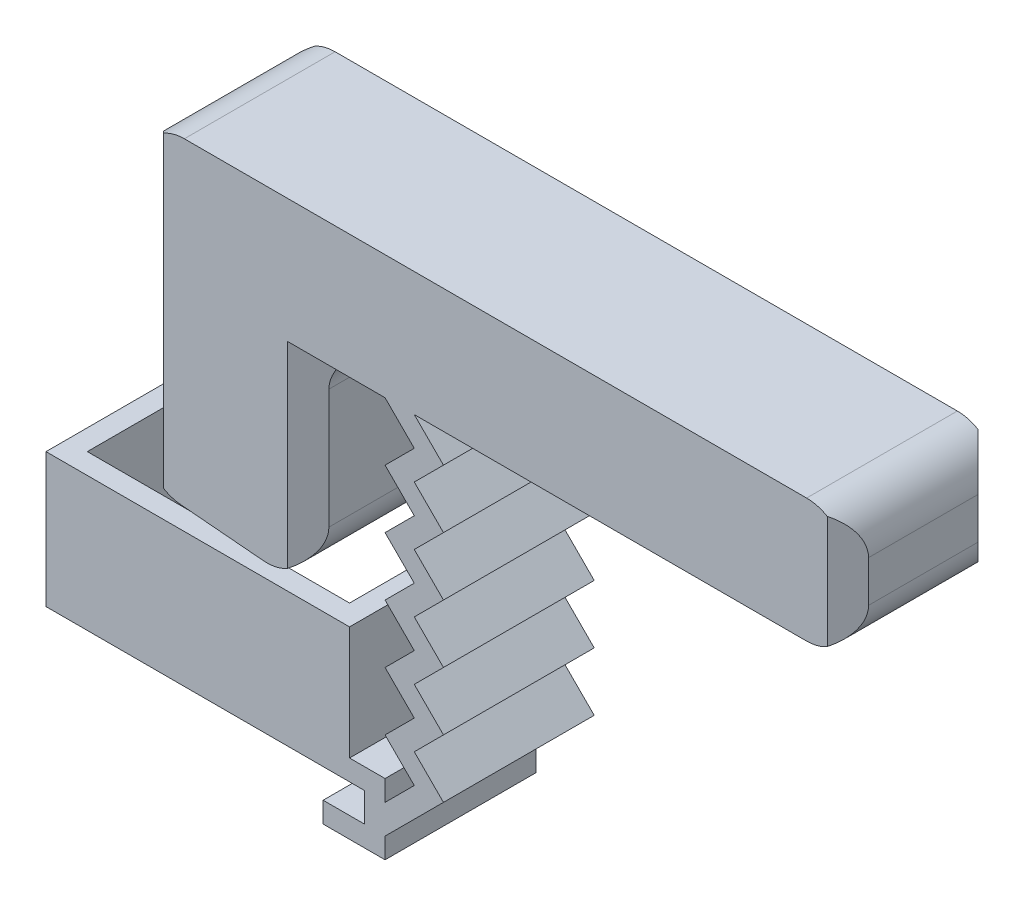
SolidWorks part; units mm, degrees
ref_plane "Front Plane" through (0, 0, 0) normal (0, 0, 1) x (1, 0, 0)
ref_plane "Top Plane" through (0, 0, 0) normal (0, 1, 0) x (1, 0, 0)
ref_plane "Right Plane" through (0, 0, 0) normal (1, 0, 0) x (0, 0, -1)
sketch "Sketch2" plane through (0, 0, 0) normal (0, 1, 0) x (1, 0, 0)
  line L0 (30.215, 56.2321) -> (30.215, 50.4321) construction
  line L1 (30.215, 50.4321) -> (17.515, 50.4321) construction
  line L2 (17.515, 50.4321) -> (17.515, 56.2321) construction
  line L3 (30.215, 56.2321) -> (30.215, 50.4321)
  line L4 (30.215, 50.4321) -> (17.515, 50.4321)
  line L5 (17.515, 50.4321) -> (17.515, 56.2321)
  line L6 (31.215, 56.7321) -> (31.215, 49.4321)
  line L7 (31.215, 49.4321) -> (16.515, 49.4321)
  line L8 (16.515, 49.4321) -> (16.515, 56.7321)
  line L11 (30.215, 56.2321) -> (29.215, 56.7321)
  line L12 (29.215, 56.7321) -> (31.215, 56.7321)
  line L14 (31.215, 56.2321) -> (31.215, 49.4321) construction
  line L15 (16.515, 49.4321) -> (16.515, 56.2321) construction
  line L16 (17.515, 56.2321) -> (18.515, 56.7321)
  line L17 (18.515, 56.7321) -> (16.515, 56.7321)
  point P2 (29.215, 56.9636)
  dimension "D2" = 1
  dimension "D3" = 0.5
  dimension "D1" = 1
extrude "Boss-Extrude3" add sketch "Sketch2" along normal blind 6.5 contours L6 L7 L8 L17 L16 L5 L4 L3 L11 L12
sketch "Sketch1" plane through (-49.4321, 0, -49.4321) normal (0, 0, 1) x (1, 0, 0)
  line L27 (82.3671, 0) -> (83.7813, 1.4142)
  line L28 (83.7813, 1.4142) -> (82.3671, 2.8284)
  line L31 (79.3671, -1.41) -> (81.3671, -1.41)
  line L32 (81.3671, -1.41) -> (81.3671, 0)
  line L33 (81.3671, 0) -> (80.6471, 0)
  line L34 (81.3671, 0) -> (61.0471, 0) construction
  line L35 (82.3671, 14.1421) -> (83.7813, 15.5563)
  line L36 (81.3671, -1.51) -> (81.3671, 0) construction
  line L37 (79.3671, -2.41) -> (82.3671, -2.41)
  line L38 (82.3671, -2.41) -> (82.3671, -1.4142)
  line L39 (82.3671, 1) -> (80.6471, 1)
  line L40 (79.3671, -1.41) -> (79.3671, -2.41)
  line L41 (80.6471, 1) -> (80.6471, 0)
  line L42 (82.3671, 2.8284) -> (83.7813, 4.2426)
  line L43 (83.7813, 4.2426) -> (82.3671, 5.6569)
  line L44 (82.3671, 5.6569) -> (83.7813, 7.0711)
  line L45 (83.7813, 7.0711) -> (82.3671, 8.4853)
  line L46 (82.3671, 8.4853) -> (83.7813, 9.8995)
  line L47 (83.7813, 9.8995) -> (82.3671, 11.3137)
  line L48 (82.3671, 11.3137) -> (83.7813, 12.7279)
  line L49 (83.7813, 12.7279) -> (82.3671, 14.1421)
  line L50 (82.3671, -1.4142) -> (85.1955, 1.4142)
  line L52 (83.7813, 2.8284) -> (85.1955, 4.2426)
  line L53 (85.1955, 4.2426) -> (83.7813, 5.6569)
  line L54 (83.7813, 5.6569) -> (85.1955, 7.0711)
  line L55 (85.1955, 7.0711) -> (83.7813, 8.4853)
  line L56 (83.7813, 8.4853) -> (85.1955, 9.8995)
  line L57 (85.1955, 9.8995) -> (83.7813, 11.3137)
  line L58 (83.7813, 11.3137) -> (85.1955, 12.7279)
  line L59 (104.7813, 16.9706) -> (83.7813, 16.9706)
  line L60 (82.8509, -0.9304) -> (85.1955, 1.4142) construction
  line L61 (83.7813, 15.5563) -> (82.3671, 16.9706)
  line L62 (85.1955, 1.4142) -> (83.7813, 2.8284)
  line L63 (83.7813, 2.8284) -> (85.1955, 4.2426)
  line L64 (85.1955, 12.7279) -> (83.0742, 14.8492) construction
  line L65 (85.1955, 4.2426) -> (83.7813, 5.6569)
  line L66 (83.7813, 5.6569) -> (85.1955, 7.0711)
  line L67 (85.1955, 7.0711) -> (83.7813, 8.4853)
  line L68 (83.7813, 8.4853) -> (85.1955, 9.8995)
  line L69 (85.1955, 9.8995) -> (83.7813, 11.3137)
  line L70 (83.7813, 11.3137) -> (85.1955, 12.7279)
  line L71 (85.1955, 12.7279) -> (83.7813, 14.1421)
  line L72 (83.7813, 14.1421) -> (85.1955, 15.5563)
  line L73 (85.1955, 15.5563) -> (83.7813, 16.9706)
  line L74 (85.1955, 15.5563) -> (83.0742, 17.6777) construction
  line L75 (82.1438, -0.2233) -> (83.7813, 1.4142) construction
  line L77 (82.8509, -0.9304) -> (85.1955, 1.4142) construction
  line L78 (78.6471, 16.9706) -> (78.6471, 7)
  line L79 (78.6471, 7) -> (70.6471, 7.6999)
  line L80 (70.6471, 7.6999) -> (70.6471, 22.9706)
  line L81 (70.6471, 22.9706) -> (104.7813, 22.9706)
  line L82 (104.7813, 22.9706) -> (104.7813, 16.9706)
  line L83 (82.3671, 16.9706) -> (78.6471, 16.9706)
  line L84 (82.3671, 0) -> (82.3671, 1)
  line L85 (82.3671, -2.41) -> (82.3671, 1) construction
  line L86 (85.1955, 1.4142) -> (83.7813, 2.8284) construction
  point P8 (105.7381, 16.9706)
  point P60 (70.6471, 10.3146)
  point P61 (105.9033, 19.9706)
  point P63 (108.4992, 22.2202)
  point P66 (104.8124, 16.9706)
  line M42 (80.6471, 0) -> (80.6471, 6.5)
  dimension "D3" = 0.1
  dimension "D4" = 2
  dimension "D6" = 45
  dimension "D7" = 90
  dimension "D9" = 1
  dimension "D10" = 4
  dimension "D11" = 85
  dimension "D12" = 1
  dimension "D13" = 8
  dimension "D14" = 0.5
  dimension "D15" = 6
  dimension "D16" = 21
  dimension "D2" = 1
  dimension "D5" = 1
  dimension "D8" = 1
  dimension "D1" = 6
extrude "Boss-Extrude4" add sketch "Sketch1" against normal up to surface (7.3 mm away) contours L27 L84 L39 L33 L32 L31 L40 L37 L38 L50 L62 L52 L53 L54 L55 L56 L57 L58 L71 L72 L73 L59 L82 L81 L80 L79 L78 L83 L61 L35 L49 L48 L47 L46 L45 L44 L43 L42 L28 M42 region at (33.9429, 0.4063, -49.4321) up to face at (30.215, 3.25, -56.7321)
chamfer "Chamfer1" distance 1 angle 45 6 edges at (21.215, 15.3352, -49.4321) (29.215, 11.9853, -49.4321) (29.215, 11.9853, -56.7321) (21.215, 15.3352, -56.7321) (55.3492, 19.9706, -49.4321) (55.3492, 19.9706, -56.7321)
fillet "Fillet1" radius 2 6 edges at (29.215, 7, -53.0821) (29.215, 16.9706, -53.0821) (21.215, 7.6999, -53.0821) (21.215, 22.9706, -53.0821) (55.3492, 16.9706, -53.0821) (55.3492, 22.9706, -53.0821)
